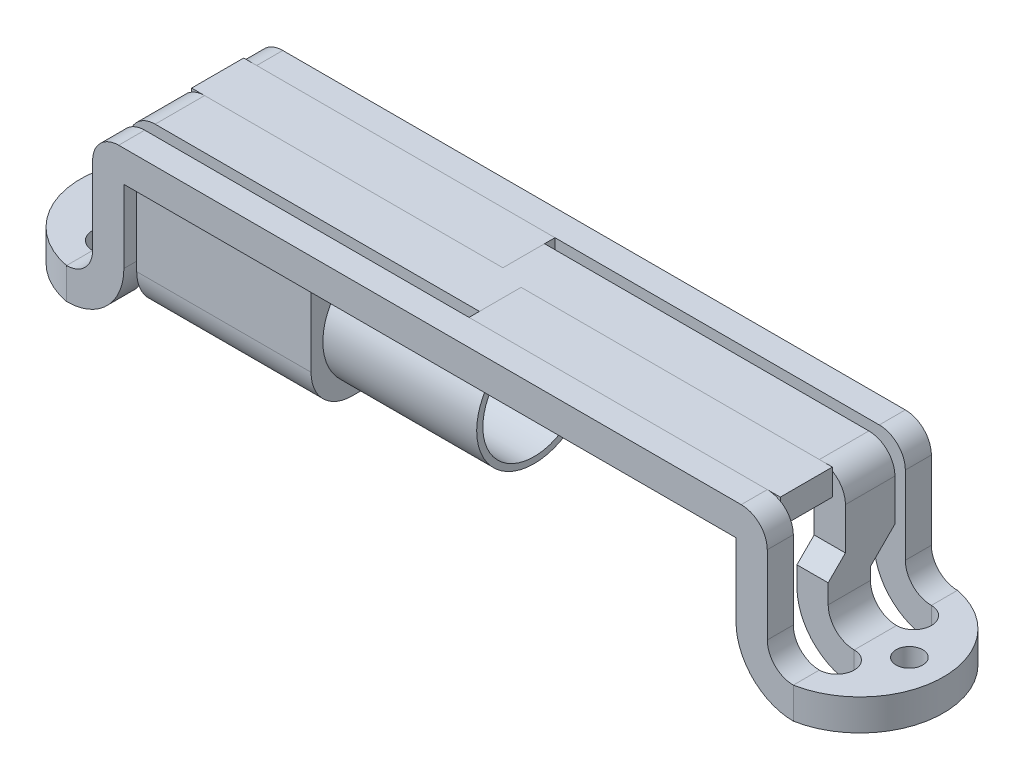
SolidWorks part; units mm, degrees
material "6061-T6 (SS)"
ref_plane "Front Plane" through (0, 0, 0) normal (0, 0, 1) x (1, 0, 0)
ref_plane "Top Plane" through (0, 0, 0) normal (0, 1, 0) x (1, 0, 0)
ref_plane "Right Plane" through (0, 0, 0) normal (1, 0, 0) x (0, 0, -1)
sketch "Sketch1" plane through (0, 0, 0) normal (0, 0, 1) x (1, 0, 0)
  line L0 (-30.353, 0) -> (30.353, 0)
  line L1 (-32.893, -2.54) -> (-32.893, -10.16)
  line L2 (-35.433, -12.7) -> (-42.0688, -12.7)
  line L3 (0, 0) -> (0, -13.9437) construction
  line L4 (35.433, -12.7) -> (42.0688, -12.7)
  line L5 (32.893, -2.54) -> (32.893, -10.16)
  arc A0 (35.433, -12.7) -> (32.893, -10.16) centre (35.433, -10.16) cw
  arc A1 (30.353, 0) -> (32.893, -2.54) centre (30.353, -2.54) cw
  arc A2 (-30.353, 0) -> (-32.893, -2.54) centre (-30.353, -2.54) ccw
  arc A3 (-32.893, -10.16) -> (-35.433, -12.7) centre (-35.433, -10.16) cw
  point P2 (0, 0)
  point P12 (32.893, -12.7)
  point P15 (32.893, 0)
  point P18 (-32.893, 0)
  point P21 (-32.893, -12.7)
  dimension "D4" = 2.54
  dimension "D1" = 84.1375
  dimension "D2" = 65.786
  dimension "D3" = 12.7
extrude "Extrude-Thin1" add sketch "Sketch1" against normal blind 16.002 thin thin type one direction wall 3.048
sketch "Sketch2" plane through (0, 0, 0) normal (0, 1, 0) x (1, 0, 0)
  line L0 (-35.433, 16.002) -> (-42.0688, 16.002)
  line L1 (-42.0688, 16.002) -> (-42.0688, 0)
  line L2 (-42.0688, 0) -> (-35.433, 0)
  line L3 (35.433, 0) -> (42.0688, 0)
  line L4 (42.0688, 0) -> (42.0688, 16.002)
  line L5 (42.0688, 16.002) -> (35.433, 16.002)
  line L6 (-42.0688, 8.001) -> (-35.433, 8.001) construction
  line L7 (-35.433, 16.002) -> (-35.433, 0) construction
  line L8 (-35.433, 8.001) -> (35.433, 8.001) construction
  line L9 (35.433, 16.002) -> (35.433, 0) construction
  line L10 (35.433, 8.001) -> (42.0688, 8.001) construction
  line L11 (-35.433, 16.002) -> (-35.433, 13.462) construction
  line L12 (-35.433, 13.462) -> (-1.27, 13.462)
  line L13 (-1.27, 13.462) -> (0, 13.462)
  line L14 (0, 0) -> (0, 16.002) construction
  line L15 (-30.353, 16.002) -> (30.353, 16.002) construction
  line L16 (0, 13.462) -> (35.433, 13.462)
  line L18 (-32.893, 8.382) -> (-1.27, 8.382)
  line L19 (-1.27, 8.382) -> (-1.27, 12.446)
  line L20 (-35.433, 2.54) -> (-35.433, 4.24) construction
  line L21 (-35.433, 13.462) -> (-35.433, 11.762) construction
  line L22 (-35.433, 10.062) -> (-32.893, 10.062)
  line L23 (-32.893, 16.002) -> (-32.893, 0) construction
  line L24 (-32.893, 10.062) -> (-32.893, 8.382)
  line L25 (-35.433, 5.94) -> (-32.893, 5.94)
  line L26 (0, 2.54) -> (-35.433, 2.54)
  line L27 (-32.893, 3.556) -> (1.27, 3.556)
  line L28 (1.27, 2.54) -> (0, 2.54)
  line L29 (1.27, 7.62) -> (1.27, 3.556)
  line L30 (35.433, 2.54) -> (1.27, 2.54)
  line L31 (32.893, 7.62) -> (1.27, 7.62)
  line L32 (35.433, 13.462) -> (35.433, 11.762) construction
  line L33 (35.433, 2.54) -> (35.433, 4.24) construction
  line L34 (35.433, 10.062) -> (32.893, 10.062)
  line L35 (32.893, 16.002) -> (32.893, 0) construction
  line L36 (32.893, 10.062) -> (32.893, 12.446)
  line L37 (35.433, 5.94) -> (32.893, 5.94)
  line L38 (32.893, 5.94) -> (32.893, 7.62)
  line L39 (-32.893, 5.94) -> (-32.893, 3.556)
  line L40 (32.893, 12.446) -> (-1.27, 12.446)
  arc A0 (-35.433, 16.002) -> (-35.433, 0) centre (-33.9273, 8.001) ccw
  arc A1 (35.433, 16.002) -> (35.433, 0) centre (33.9273, 8.001) cw
  circle A2 centre (-38.7509, 8.001) radius 1.3
  circle A3 centre (38.7509, 8.001) radius 1.3
  arc A6 (-35.433, 5.94) -> (-35.433, 2.54) centre (-35.433, 4.24) ccw
  arc A7 (-35.433, 13.462) -> (-35.433, 10.062) centre (-35.433, 11.762) ccw
  arc A10 (35.433, 10.062) -> (35.433, 13.462) centre (35.433, 11.762) ccw
  arc A11 (35.433, 2.54) -> (35.433, 5.94) centre (35.433, 4.24) ccw
  line M4 (30.353, 0) -> (30.353, 16.002)
  line M6 (-30.353, 16.002) -> (-30.353, 0)
  dimension "D4" = 2.6
  dimension "D1" = 2.54
  dimension "D2" = 1.27
  dimension "D3" = 5.08
extrude "Cut-Extrude1" cut sketch "Sketch2" against normal through all contours A0 L0 L1 | A0 L1 L2 | L18 L12 M6 | L18 L19 L16 L13 L12 M4 M6 | L31 L29 L27 L26 L28 L30 M4 M6 | L31 L30 M4 | A3 | L4 A1 L3 | L5 A1 L4 | L16 M4 | L26 L27 M6 | A2 | L19 L40 L36 L34 A10 L16 L13 L12 A7 L22 L24 L18 region at (-40.3835, 0, -14.1912) region at (-40.3835, 0, -1.8108) region at (40.3835, 0, -1.8108) region at (40.3835, 0, -14.1912) region at (-33.2529, 0, -11.3464) region at (-10.3898, 0, -11.285) region at (-34.3208, 0, -4.0448) region at (10.3898, 0, -4.717) region at (34.3208, 0, -11.9572) region at (33.2529, 0, -4.6556) region at (-38.7509, 0, -8.001) region at (38.7509, 0, -8.001)
sketch "Sketch3" plane through (0, 0, 0) normal (0, 1, 0) x (1, 0, 0)
  line L0 (-32.893, 13.462) -> (-30.353, 13.462) construction
  line L1 (-1.27, 8.382) -> (-31.623, 8.382)
  line L2 (-1.27, 8.382) -> (-1.27, 13.462)
  line L3 (-1.27, 13.462) -> (-31.623, 13.462)
  line L4 (-31.623, 8.382) -> (-31.623, 13.462)
  line L6 (1.27, 7.62) -> (31.623, 7.62)
  line L7 (1.27, 7.62) -> (1.27, 2.54)
  line L8 (1.27, 2.54) -> (31.623, 2.54)
  line L9 (31.623, 7.62) -> (31.623, 2.54)
  line L10 (32.893, 2.54) -> (30.353, 2.54) construction
extrude "Boss-Extrude1" add sketch "Sketch3" against normal blind 2.54 separate body
sketch "Sketch4" plane through (0, 0, 0) normal (0, 1, 0) x (1, 0, 0)
  line L0 (0, 0) -> (0, 16.002) construction
  line L1 (-30.353, 16.002) -> (30.353, 16.002) construction
  line L21 (-32.893, 17.272) -> (-35.5471, 17.272)
  line L22 (-35.5471, -1.27) -> (-32.893, -1.27)
  line L23 (-32.893, -1.27) -> (-30.353, -1.27)
  line L24 (-30.353, -1.27) -> (30.353, -1.27)
  line L25 (30.353, -1.27) -> (32.893, -1.27)
  line L26 (32.893, -1.27) -> (35.5471, -1.27)
  line L27 (35.5471, 17.272) -> (32.893, 17.272)
  line L28 (32.893, 17.272) -> (30.353, 17.272)
  line L29 (-30.353, 17.272) -> (30.353, 17.272)
  line L30 (-30.353, 17.272) -> (-32.893, 17.272)
  line L32 (-43.3388, 8.001) -> (43.3388, 8.001) construction
  arc A4 (-35.5471, 17.272) -> (-35.5471, -1.27) centre (-33.9273, 8.001) ccw
  arc A5 (35.5471, -1.27) -> (35.5471, 17.272) centre (33.9273, 8.001) ccw
sketch "Sketch6" plane through (0, 0, -8.382) normal (0, 0, -1) x (-1, 0, 0)
  line L0 (32.893, -10.16) -> (32.893, -2.54) construction
  line L1 (32.893, -15.1374) -> (32.893, -10.16) construction
  line L2 (29.845, -3.048) -> (29.845, -10.16) construction
  line L3 (32.893, -10.16) -> (32.893, -6.604)
  line L4 (32.893, -15.1374) -> (32.893, -10.16)
  line L5 (29.845, -6.604) -> (29.845, -10.16)
  line L7 (32.893, -10.16) -> (32.893, -6.604) construction
  line L8 (32.893, -6.604) -> (29.845, -6.604)
  arc A0 (29.845, -10.16) -> (32.893, -15.1374) centre (35.433, -10.16) ccw construction
  arc A1 (29.845, -10.16) -> (32.893, -15.1374) centre (35.433, -10.16) ccw
extrude "Boss-Extrude2" add sketch "Sketch6" along normal up to surface (1.68 mm away) up to face at (-34.0224, -13.6055, -10.062)
sketch "Sketch7" plane through (0, 0, -7.62) normal (0, 0, 1) x (1, 0, 0)
  line L0 (32.893, -10.16) -> (32.893, -2.54) construction
  line L1 (32.893, -15.1374) -> (32.893, -10.16) construction
  line L2 (29.845, -3.048) -> (29.845, -10.16) construction
  line L3 (32.893, -10.16) -> (32.893, -6.6)
  line L4 (32.893, -15.1374) -> (32.893, -10.16)
  line L5 (29.845, -6.604) -> (29.845, -10.16)
  line L6 (32.893, -10.16) -> (32.893, -6.6) construction
  line L7 (32.893, -6.6) -> (29.845, -6.604)
  arc A0 (29.845, -10.16) -> (32.893, -15.1374) centre (35.433, -10.16) ccw construction
  arc A1 (29.845, -10.16) -> (32.893, -15.1374) centre (35.433, -10.16) ccw
extrude "Boss-Extrude3" add sketch "Sketch7" along normal up to surface (1.68 mm away) up to face at (34.0224, -13.6055, -5.94)
sketch "Sketch8" plane through (0, 0, -12.446) normal (0, 0, -1) x (-1, 0, 0)
  line L0 (-32.893, -15.1374) -> (-32.893, -2.54) construction
  line L1 (-29.845, -3.048) -> (-29.845, -10.16) construction
  line L2 (-32.893, -15.1374) -> (-32.893, -6.6)
  line L3 (-29.845, -6.604) -> (-29.845, -10.16)
  line L4 (-29.845, -6.604) -> (-32.893, -6.6)
  arc A0 (-32.893, -15.1374) -> (-29.845, -10.16) centre (-35.433, -10.16) ccw construction
  arc A1 (-32.893, -15.1374) -> (-29.845, -10.16) centre (-35.433, -10.16) ccw
extrude "Cut-Extrude2" cut sketch "Sketch8" against normal up to surface (2.384 mm away) up to face at (34.0224, -13.6055, -10.062)
sketch "Sketch9" plane through (0, 0, -3.556) normal (0, 0, 1) x (1, 0, 0)
  line L0 (-32.893, -15.1374) -> (-32.893, -2.54) construction
  line L1 (-29.845, -3.048) -> (-29.845, -10.16) construction
  line L2 (-32.893, -15.1374) -> (-32.893, -6.604)
  line L3 (-29.845, -6.604) -> (-29.845, -10.16)
  line L4 (-32.893, -6.604) -> (-29.845, -6.604)
  arc A0 (-32.893, -15.1374) -> (-29.845, -10.16) centre (-35.433, -10.16) ccw construction
  arc A1 (-32.893, -15.1374) -> (-29.845, -10.16) centre (-35.433, -10.16) ccw
extrude "Cut-Extrude3" cut sketch "Sketch9" against normal up to surface (2.384 mm away) up to face at (-34.0224, -13.6055, -5.94)
chamfer "Chamfer1" distance 1.7 angle 45 2 edges at (-31.369, -6.604, -10.062) (31.369, -6.602, -5.94)
chamfer "Chamfer2" distance 2.38 angle 45 2 edges at (-31.369, -6.604, -5.94) (31.369, -6.602, -10.062)
sketch "Sketch10" plane through (0, -3.048, 0) normal (0, -1, 0) x (1, 0, 0)
  line L0 (-29.845, 0) -> (-29.845, -16.002) construction
  line L1 (-29.845, -1.251) -> (-29.845, -14.751)
  line L2 (-29.845, -1.251) -> (-12.845, -1.251)
  line L3 (-12.845, -1.251) -> (-12.845, -14.751)
  line L4 (-12.845, -14.751) -> (-29.845, -14.751)
  point P7 (-29.845, -8.001)
  dimension "D1" = 13.5
  dimension "D2" = 17
extrude "Boss-Extrude4" add sketch "Sketch10" along normal blind 12
sketch "Sketch11" plane through (-12.845, 0, 0) normal (1, 0, 0) x (0, 0, -1)
  line L0 (14.751, -15.048) -> (1.251, -3.048) construction
  circle A0 centre (8.001, -9.048) radius 5.6
  circle A1 centre (8.001, -9.048) radius 5
extrude "Boss-Extrude5" add sketch "Sketch11" along normal blind 15
fillet "Fillet1" radius 4 2 edges at (-21.345, -15.048, -1.251) (-21.345, -15.048, -14.751)
